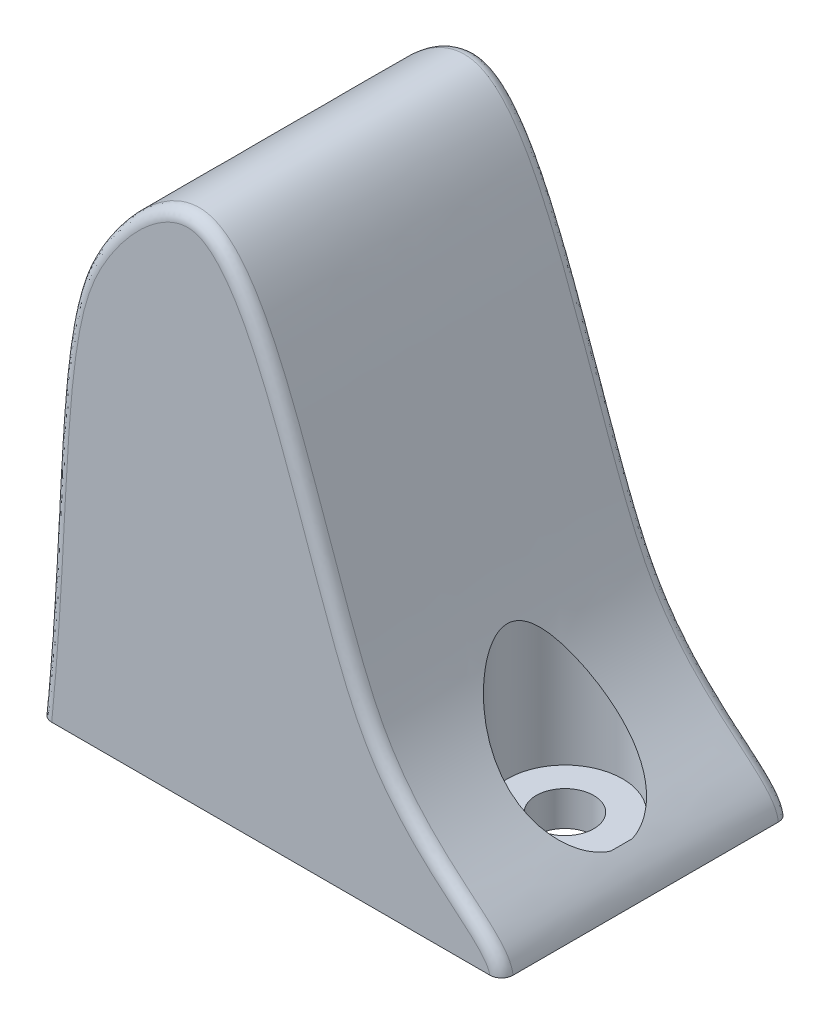
SolidWorks part; units mm, degrees
ref_plane "Front Plane" through (0, 0, 0) normal (0, 0, 1) x (1, 0, 0)
ref_plane "Top Plane" through (0, 0, 0) normal (0, 1, 0) x (1, 0, 0)
ref_plane "Right Plane" through (0, 0, 0) normal (1, 0, 0) x (0, 0, -1)
sketch "Sketch1" plane through (0, 0, 0) normal (0, 0, 1) x (1, 0, 0)
  line L0 (0, 0) -> (40, 0)
  line L1 (55, 0) -> (-55, 0) construction
  spline S1 degree 3 poles (0, 0) (1.5328, 15.0608) (0.8338, 29.6024) (6.1686, 40.3521) (16.5522, 50.1479) (22.5425, 28.1723) (31.4017, 5.7792) (39.6476, 3.1068) (40, 0) knots 0 0 0 0 0.243956 0.28795 0.439944 0.715329 0.771335 1 1 1 1
  point P5 (13.3132, 44.0028)
  point P6 (4.273, 36.4569)
  dimension "D2" = 40
extrude "Boss-Extrude1" add sketch "Sketch1" along normal blind 25
fillet "Fillet1" radius 1 2 edges
sketch "Sketch2" plane through (0, 0, 0) normal (0, 1, 0) x (1, 0, 0)
  line L0 (-55, 0) -> (55, 0) construction
  line L2 (40, -24) -> (40, -1) construction
  circle A0 centre (33, -12.5) radius 5
  dimension "D1" = 10
  dimension "D2" = 12.5
  dimension "D3" = 7
extrude "Cut-Extrude1" cut sketch "Sketch2" along normal blind 15 from offset 3
sketch "Sketch3" plane through (0, 0, 0) normal (0, 1, 0) x (1, 0, 0)
  line L1 (-55, 0) -> (55, 0) construction
  line L2 (40, -24) -> (40, -1) construction
  circle A0 centre (33, -12.5) radius 2.5
  dimension "D1" = 5
  dimension "D2" = 7
  dimension "D3" = 12.5
extrude "Cut-Extrude2" cut sketch "Sketch3" along normal through all
